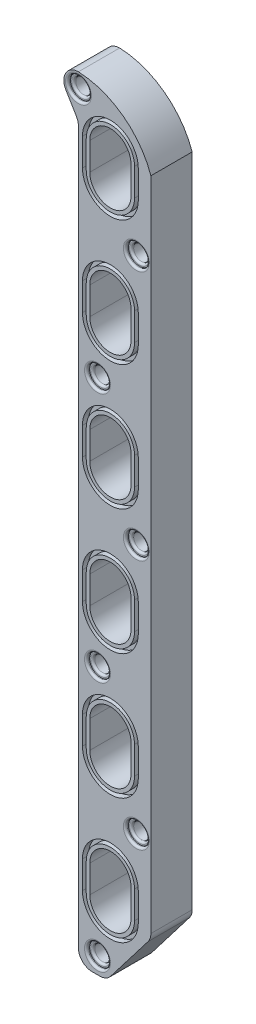
SolidWorks part; units mm, degrees
ref_plane "Front Plane" through (0, 0, 0) normal (1, 0, 0) x (0, 1, 0)
ref_plane "Top Plane" through (0, 0, 0) normal (0, 0, 1) x (0, 1, 0)
ref_plane "Right Plane" through (0, 0, 0) normal (0, 1, 0) x (-1, 0, 0)
sketch "Base_Flange_Geometry" plane through (0, 0, 0) normal (0, 0, 1) x (0, 1, 0)
  line L0 (35.5, 0) -> (55.5, 0) construction
  line L1 (35.5, 15) -> (55.5, 15)
  line L2 (35.5, -15) -> (55.5, -15)
  line L3 (126.5, 0) -> (146.5, 0) construction
  line L4 (126.5, 15) -> (146.5, 15)
  line L5 (126.5, -15) -> (146.5, -15)
  line L6 (217.5, 0) -> (237.5, 0) construction
  line L7 (217.5, 15) -> (237.5, 15)
  line L8 (217.5, -15) -> (237.5, -15)
  line L9 (20.5, 0) -> (-20.5, 0) construction
  line L10 (0, 0) -> (0, 23.25) construction
  line L11 (70.5, 0) -> (111.5, 0) construction
  line L12 (161.5, 0) -> (202.5, 0) construction
  line L13 (-217.5, 0) -> (-237.5, 0) construction
  line L14 (-217.5, 15) -> (-237.5, 15)
  line L15 (-217.5, -15) -> (-237.5, -15)
  line L16 (-161.5, 0) -> (-202.5, 0) construction
  line L17 (-70.5, 0) -> (-111.5, 0) construction
  line L18 (-126.5, 0) -> (-146.5, 0) construction
  line L19 (-126.5, 15) -> (-146.5, 15)
  line L20 (-126.5, -15) -> (-146.5, -15)
  line L21 (-35.5, 0) -> (-55.5, 0) construction
  line L22 (-35.5, 15) -> (-55.5, 15)
  line L23 (-35.5, -15) -> (-55.5, -15)
  line L24 (0, 23.25) -> (276.6, 23.25)
  line L25 (0, 23.25) -> (-285, 23.25)
  line L26 (0, 0) -> (0, -13.25) construction
  line L27 (-91, 0) -> (-91, 3.8) construction
  line L28 (91, 0) -> (91, 3.8) construction
  line L29 (182, 0) -> (182, -13.25) construction
  line L30 (-182, 0) -> (-182, -13.25) construction
  line L31 (-252.5, 0) -> (-273, 0) construction
  line L32 (-273, 0) -> (-273, 3.8) construction
  line L33 (-91, 15) -> (-91, 23.25) construction
  line L34 (91, 15) -> (91, 23.25) construction
  line L35 (-273, 15) -> (-273, 23.25) construction
  line L36 (-273, 3.8) -> (-273, 15) construction
  line L37 (-91, 3.8) -> (-91, 15) construction
  line L38 (91, 3.8) -> (91, 15) construction
  line L39 (0, -13.25) -> (0, -24.45) construction
  line L40 (-182, -13.25) -> (-182, -24.45) construction
  line L41 (182, -13.25) -> (182, -24.45) construction
  line L42 (0, -24.45) -> (0, -29.45) construction
  line L43 (-285, 23.25) -> (-285, -29.45)
  line L44 (-285, -29.45) -> (0, -29.45)
  line L45 (266, 23.25) -> (266, -18.85) construction
  line L46 (266, -18.85) -> (182, -18.85) construction
  line L47 (260.5456, 32.339) -> (245.4, 23.25)
  line L48 (217.5, 17.55) -> (237.5, 17.55)
  line L49 (217.5, -17.55) -> (237.5, -17.55)
  line L50 (126.5, 17.55) -> (146.5, 17.55)
  line L51 (126.5, -17.55) -> (146.5, -17.55)
  line L52 (35.5, 17.55) -> (55.5, 17.55)
  line L53 (35.5, -17.55) -> (55.5, -17.55)
  line L54 (-35.5, 17.55) -> (-55.5, 17.55)
  line L55 (-35.5, -17.55) -> (-55.5, -17.55)
  line L56 (-126.5, 17.55) -> (-146.5, 17.55)
  line L57 (-126.5, -17.55) -> (-146.5, -17.55)
  line L58 (-217.5, 17.55) -> (-237.5, 17.55)
  line L59 (-217.5, -17.55) -> (-237.5, -17.55)
  line L60 (-217.5, 20.3) -> (-237.5, 20.3)
  line L61 (-217.5, -20.3) -> (-237.5, -20.3)
  line L62 (-126.5, 20.3) -> (-146.5, 20.3)
  line L63 (-126.5, -20.3) -> (-146.5, -20.3)
  line L64 (-35.5, 20.3) -> (-55.5, 20.3)
  line L65 (-35.5, -20.3) -> (-55.5, -20.3)
  line L66 (35.5, 20.3) -> (55.5, 20.3)
  line L67 (35.5, -20.3) -> (55.5, -20.3)
  line L68 (126.5, 20.3) -> (146.5, 20.3)
  line L69 (126.5, -20.3) -> (146.5, -20.3)
  line L70 (217.5, 20.3) -> (237.5, 20.3)
  line L71 (217.5, -20.3) -> (237.5, -20.3)
  line L73 (237.5, -29.45) -> (0, -29.45)
  line L74 (237.5, -29.45) -> (237.5, -20.3) construction
  arc A0 (35.5, 15) -> (35.5, -15) centre (35.5, 0) ccw
  arc A1 (55.5, -15) -> (55.5, 15) centre (55.5, 0) ccw
  arc A2 (126.5, 15) -> (126.5, -15) centre (126.5, 0) ccw
  arc A3 (146.5, -15) -> (146.5, 15) centre (146.5, 0) ccw
  arc A4 (217.5, 15) -> (217.5, -15) centre (217.5, 0) ccw
  arc A5 (237.5, -15) -> (237.5, 15) centre (237.5, 0) ccw
  arc A6 (-217.5, 15) -> (-217.5, -15) centre (-217.5, 0) cw
  arc A7 (-237.5, -15) -> (-237.5, 15) centre (-237.5, 0) cw
  arc A8 (-126.5, 15) -> (-126.5, -15) centre (-126.5, 0) cw
  arc A9 (-146.5, -15) -> (-146.5, 15) centre (-146.5, 0) cw
  arc A10 (-35.5, 15) -> (-35.5, -15) centre (-35.5, 0) cw
  arc A11 (-55.5, -15) -> (-55.5, 15) centre (-55.5, 0) cw
  circle A12 centre (-182, -18.85) radius 5.6
  circle A13 centre (-91, 9.4) radius 5.6
  circle A14 centre (0, -18.85) radius 5.6
  circle A15 centre (91, 9.4) radius 5.6
  circle A16 centre (182, -18.85) radius 5.6
  circle A17 centre (-273, 9.4) radius 5.6
  circle A18 centre (266, 23.25) radius 5.6
  circle A19 centre (266, 23.25) radius 10.6
  arc A20 (237.5, -17.55) -> (237.5, 17.55) centre (237.5, 0) ccw
  arc A21 (217.5, 17.55) -> (217.5, -17.55) centre (217.5, 0) ccw
  arc A22 (146.5, -17.55) -> (146.5, 17.55) centre (146.5, 0) ccw
  arc A23 (126.5, 17.55) -> (126.5, -17.55) centre (126.5, 0) ccw
  arc A24 (55.5, -17.55) -> (55.5, 17.55) centre (55.5, 0) ccw
  arc A25 (35.5, 17.55) -> (35.5, -17.55) centre (35.5, 0) ccw
  arc A26 (-55.5, -17.55) -> (-55.5, 17.55) centre (-55.5, 0) cw
  arc A27 (-35.5, 17.55) -> (-35.5, -17.55) centre (-35.5, 0) cw
  arc A28 (-146.5, -17.55) -> (-146.5, 17.55) centre (-146.5, 0) cw
  arc A29 (-126.5, 17.55) -> (-126.5, -17.55) centre (-126.5, 0) cw
  arc A30 (-237.5, -17.55) -> (-237.5, 17.55) centre (-237.5, 0) cw
  arc A31 (-217.5, 17.55) -> (-217.5, -17.55) centre (-217.5, 0) cw
  arc A32 (-237.5, -20.3) -> (-237.5, 20.3) centre (-237.5, 0) cw
  arc A33 (-217.5, 20.3) -> (-217.5, -20.3) centre (-217.5, 0) cw
  arc A34 (-146.5, -20.3) -> (-146.5, 20.3) centre (-146.5, 0) cw
  arc A35 (-126.5, 20.3) -> (-126.5, -20.3) centre (-126.5, 0) cw
  arc A36 (-55.5, -20.3) -> (-55.5, 20.3) centre (-55.5, 0) cw
  arc A37 (-35.5, 20.3) -> (-35.5, -20.3) centre (-35.5, 0) cw
  arc A38 (55.5, -20.3) -> (55.5, 20.3) centre (55.5, 0) ccw
  arc A39 (35.5, 20.3) -> (35.5, -20.3) centre (35.5, 0) ccw
  arc A40 (146.5, -20.3) -> (146.5, 20.3) centre (146.5, 0) ccw
  arc A41 (126.5, 20.3) -> (126.5, -20.3) centre (126.5, 0) ccw
  arc A42 (237.5, -20.3) -> (237.5, 20.3) centre (237.5, 0) ccw
  arc A43 (217.5, 20.3) -> (217.5, -20.3) centre (217.5, 0) ccw
  arc A44 (276.6, 23.25) -> (237.5, -29.45) centre (218.2427, 25.6925) cw
  point P3 (45.5, 0)
  point P11 (136.5, 0)
  point P16 (227.5, 0)
  point P24 (0, 0)
  point P33 (-227.5, 0)
  point P44 (-136.5, 0)
  point P51 (-45.5, 0)
  dimension "D9" = 11.2
  dimension "D2" = 41
  dimension "D3" = 30
  dimension "D4" = 50
  dimension "D5" = 23.25
  dimension "D6" = 285
  dimension "D7" = 20.5
  dimension "D8" = 8.25
  dimension "D10" = 36.5
  dimension "D11" = 5
  dimension "D12" = 84
  dimension "D14" = 10
  dimension "D17" = 6
  dimension "D13" = 5
  dimension "D15" = 2.55
  dimension "D16" = 5.3
extrude "Boss-Extrude1" add sketch "Base_Flange_Geometry" along normal blind 4.35 contours A44 A19 L24 L25 L43 L44 L73 A43 L70 A42 L71 A41 L68 A40 L69 A39 L66 A38 L67 L62 A35 L63 A34 A17 A16 A15 A14 A13 A12 L60 A33 L61 A32 L64 A37 L65 A36 | L52 A25 L53 A24 A1 L2 A0 L1 | A27 L54 A26 L55 L23 A11 L22 A10 | L50 A23 L51 A22 A3 L5 A2 L4 | L48 A21 L49 A20 A5 L8 A4 L7 | A19 L47 L24 | L24 A19 A18 | L24 A19 A18 | A29 L56 A28 L57 L20 A9 L19 A8 | A31 L58 A30 L59 L15 A7 L14 A6 region at (-22.686, 122.7, 0) region at (-25.7939, 252.7739, 0) region at (-28.3555, 256.9819, 0) region at (-23.013, 257.9, 0) region at (-16.8967, 227.5, 0) region at (-16.8967, 136.5, 0) region at (-16.8967, 45.5, 0) region at (0, -18.6033, 0) region at (0, -109.6033, 0) region at (0, -200.6033, 0)
extrude "Boss-Extrude2" add sketch "Base_Flange_Geometry<5>" against normal blind 25.65 contours A44 A19 L24 L25 L43 L44 L73 A43 L70 A42 L71 A41 L68 A40 L69 A39 L66 A38 L67 L62 A35 L63 A34 A17 A16 A15 A14 A13 A12 L60 A33 L61 A32 L64 A37 L65 A36 | L70 A43 L71 A42 A21 L48 A20 L49 | L48 A21 L49 A20 A5 L8 A4 L7 | L24 A19 A18 | A19 L47 L24 | L24 A19 A18 | L50 A23 L51 A22 A3 L5 A2 L4 | L68 A41 L69 A40 A23 L50 A22 L51 | L52 A25 L53 A24 A1 L2 A0 L1 | L66 A39 L67 A38 A25 L52 A24 L53 | A27 L54 A26 L55 L23 A11 L22 A10 | A37 L64 A36 L65 L54 A27 L55 A26 | A29 L56 A28 L57 L20 A9 L19 A8 | A35 L62 A34 L63 L56 A29 L57 A28 | A31 L58 A30 L59 L15 A7 L14 A6 | A33 L60 A32 L61 L58 A31 L59 A30 region at (-22.686, 122.7, 0) region at (-25.7939, 252.7739, 0) region at (-28.3555, 256.9819, 0) region at (-23.013, 257.9, 0) region at (-16.8967, 227.5, 0) region at (-16.8967, 136.5, 0) region at (-16.8967, 45.5, 0) region at (0, -18.6033, 0) region at (0, -109.6033, 0) region at (0, -200.6033, 0) region at (0, -197.9294, 0) region at (0, -106.9294, 0) region at (0, -15.9294, 0) region at (-19.5706, 45.5, 0) region at (-19.5706, 136.5, 0) region at (-19.5706, 227.5, 0)
sketch "Base_Flange_Geometry<5>" plane through (0, 0, 0) normal (0, 0, 1) x (0, 1, 0) same geometry as "Base_Flange_Geometry"
chamfer "Chamfer1" distance 42 angle 37.5 1 edges at (29.45, -285, -10.65) first distance on face at (29.45, -23.75, -10.65)
fillet "Fillet1" radius 10 4 edges at (-2.7777, -285, -10.65) (-23.25, -285, -10.65) (-23.25, 245.4, -10.65) (29.45, -243, -10.65)
sketch "Insert_Hole_Geometry" plane through (0, 0, 4.35) normal (0, 0, 1) x (1, 0, 0)
  line L5 (0.2243, -281.0876) -> (27.3835, -245.6931)
  line L6 (29.45, -239.6055) -> (29.45, 237.5)
  line L7 (-32.339, 260.5456) -> (-24.6755, 247.7754)
  line L8 (-23.25, 242.6297) -> (-23.25, -275)
  line L9 (-13.25, -285) -> (-7.7092, -285)
  line L10 (0.2243, -281.0876) -> (27.3835, -245.6931)
  line L11 (29.45, -239.6055) -> (29.45, 237.5)
  line L12 (-32.339, 260.5456) -> (-24.6755, 247.7754)
  line L13 (-23.25, 242.6297) -> (-23.25, -275)
  line L14 (-13.25, -285) -> (-7.7092, -285)
  circle A0 centre (18.85, 182) radius 7.91
  circle A1 centre (-23.25, 266) radius 7.91
  circle A2 centre (-9.4, 91) radius 7.91
  circle A3 centre (18.85, 0) radius 7.91
  circle A4 centre (-9.4, -91) radius 7.91
  circle A5 centre (18.85, -182) radius 7.91
  arc A6 (27.3835, -245.6931) -> (29.45, -239.6055) centre (19.45, -239.6055) ccw
  arc A7 (29.45, 237.5) -> (-23.25, 276.6) centre (-25.6925, 218.2427) ccw
  arc A8 (-23.25, 276.6) -> (-32.339, 260.5456) centre (-23.25, 266) ccw
  arc A9 (-23.25, 242.6297) -> (-24.6755, 247.7754) centre (-33.25, 242.6297) ccw
  arc A10 (-23.25, -275) -> (-13.25, -285) centre (-13.25, -275) ccw
  arc A11 (-7.7092, -285) -> (0.2243, -281.0876) centre (-7.7092, -275) ccw
  arc A12 (27.3835, -245.6931) -> (29.45, -239.6055) centre (19.45, -239.6055) ccw
  arc A13 (29.45, 237.5) -> (-23.25, 276.6) centre (-25.6925, 218.2427) ccw
  arc A14 (-23.25, 276.6) -> (-32.339, 260.5456) centre (-23.25, 266) ccw
  arc A15 (-23.25, 242.6297) -> (-24.6755, 247.7754) centre (-33.25, 242.6297) ccw
  arc A16 (-23.25, -275) -> (-13.25, -285) centre (-13.25, -275) ccw
  arc A17 (-7.7092, -285) -> (0.2243, -281.0876) centre (-7.7092, -275) ccw
  circle A18 centre (-9.4, -273) radius 7.91
  circle A19 centre (-9.4, -273) radius 5.6 construction
  circle A20 centre (18.85, -182) radius 5.6 construction
  circle A21 centre (-9.4, -91) radius 5.6 construction
  circle A22 centre (18.85, 0) radius 5.6 construction
  circle A23 centre (-9.4, 91) radius 5.6 construction
  circle A24 centre (-23.25, 266) radius 5.6 construction
  circle A25 centre (18.85, 182) radius 5.6 construction
  circle A26 centre (-9.4, -273) radius 5.6
  circle A27 centre (18.85, -182) radius 5.6
  circle A28 centre (-9.4, -91) radius 5.6
  circle A29 centre (18.85, 0) radius 5.6
  circle A30 centre (-9.4, 91) radius 5.6
  circle A31 centre (-23.25, 266) radius 5.6
  circle A32 centre (18.85, 182) radius 5.6
  circle M12 centre (-23.25, 266) radius 5.6
  circle M40 centre (-9.4, -273) radius 5.6
  circle M41 centre (18.85, 182) radius 5.6
  circle M42 centre (-9.4, 91) radius 5.6
  circle M43 centre (18.85, 0) radius 5.6
  circle M44 centre (-9.4, -91) radius 5.6
  circle M45 centre (18.85, -182) radius 5.6
  dimension "D2" = 15.82
extrude "Cut-Extrude1" cut sketch "Insert_Hole_Geometry" against normal blind 2.2 contours A0 M41 | A1 M12 | A2 M42 | A3 M43 | A4 M44 | A5 M45 | A18 M40 region at (11.1637, 182, 4.35) region at (-30.9363, 266, 4.35) region at (-17.0863, 91, 4.35) region at (11.1637, 0, 4.35) region at (-17.0863, -91, 4.35) region at (11.1637, -182, 4.35) region at (-17.0863, -273, 4.35)
fillet "Fillet2" radius 1.5 14 edges at (-15.34, 266, 4.35) (26.76, 182, 4.35) (-1.49, 91, 4.35) (26.76, 0, 4.35) (-1.49, -273, 4.35) (26.76, -182, 4.35) (-1.49, -91, 4.35) (-3.8, -91, 2.15) (-3.8, -273, 2.15) (24.45, -182, 2.15) (-17.65, 266, 2.15) (24.45, 182, 2.15) (-3.8, 91, 2.15) (24.45, 0, 2.15)
sketch "Sketch3" plane through (0, 0, 0) normal (0, 1, 0) x (-1, 0, 0)
  line L0 (-29.45, -25.65) -> (23.25, -25.65) construction
  line L1 (-3.1, -25.65) -> (-118.0479, -25.65) construction
  line L2 (-118.0479, -25.65) -> (-118.0479, -236.4778) construction
  arc A0 (-3.1, -25.65) -> (-118.0479, -236.4778) centre (-223.1476, -42.4252) cw
equation "\"Port_Height\"= 30mm"
equation "\"Port_Width\" = 50mm"
equation "\"Port_Spacing\" = 41mm"
equation "\"D2@Base_Flange_Geometry\" = \"Port_Spacing\""
equation "\"D3@Base_Flange_Geometry\" = \"Port_Height\""
equation "\"D4@Base_Flange_Geometry\" = \"Port_Width\""
equation "\"Upper_Offset\"= ( \"Port_Height\" / 2 ) + 8.25"
equation "\"D5@Base_Flange_Geometry\" = \"Upper_Offset\""
equation "\"Half_Total_Length (Upper)\"= 28.5cm"
equation "\"D6@Base_Flange_Geometry\" = \"Half_Total_Length (Upper)\""
equation "\"Fastener_Size\"= 8.4mm"
equation "\"Insert_OD\"= 11.2mm"
equation "\"D7@Base_Flange_Geometry\" = \"Port_Spacing\" / 2"
equation "\"Top_Insert_Midsection_Offset\"= 8.25mm"
equation "\"D8@Base_Flange_Geometry\" = \"Top_Insert_Midsection_Offset\""
equation "\"D9@Base_Flange_Geometry\" = \"Insert_OD\""
equation "\"Bottom_Insert_TopToInsertOD_Offset\" = 36.5mm"
equation "\"D10@Base_Flange_Geometry\" = \"Bottom_Insert_TopToInsertOD_Offset\""
equation "\"Bottom_Insert_PartBottom_Offset\"= 5mm"
equation "\"D11@Base_Flange_Geometry\" = \"Bottom_Insert_PartBottom_Offset\""
equation "\"D12@Base_Flange_Geometry\" = \"Front_Insert_Fastener_Offset\""
equation "\"Front_Insert_Fastener_Offset\"= 84mm"
equation "\"Z_Offset\"= 30mm"
equation "\"Gasket_Depth\"= 4.35mm"
equation "\"D1@Boss-Extrude1\"=\"Gasket_Depth\""
equation "\"D1@Boss-Extrude2\"=\"Z_Offset\"-\"Gasket_Depth\""
equation "\"Global_Outer_Part_Fillet\"= 8mm"
equation "\"Insert_Hole_Outer_Diameter\"= 15.82mm"
equation "\"Insert_Hole_OD_Depth\"= 2.2mm"
equation "\"D2@Insert_Hole_Geometry\" = \"Insert_Hole_Outer_Diameter\""
equation "\"D1@Cut-Extrude1\"=\"Insert_Hole_OD_Depth\""
equation "\"Insert_Hole_Fillets\"= 1.5mm"
equation "\"D1@Fillet2\"=\"Insert_Hole_Fillets\""
